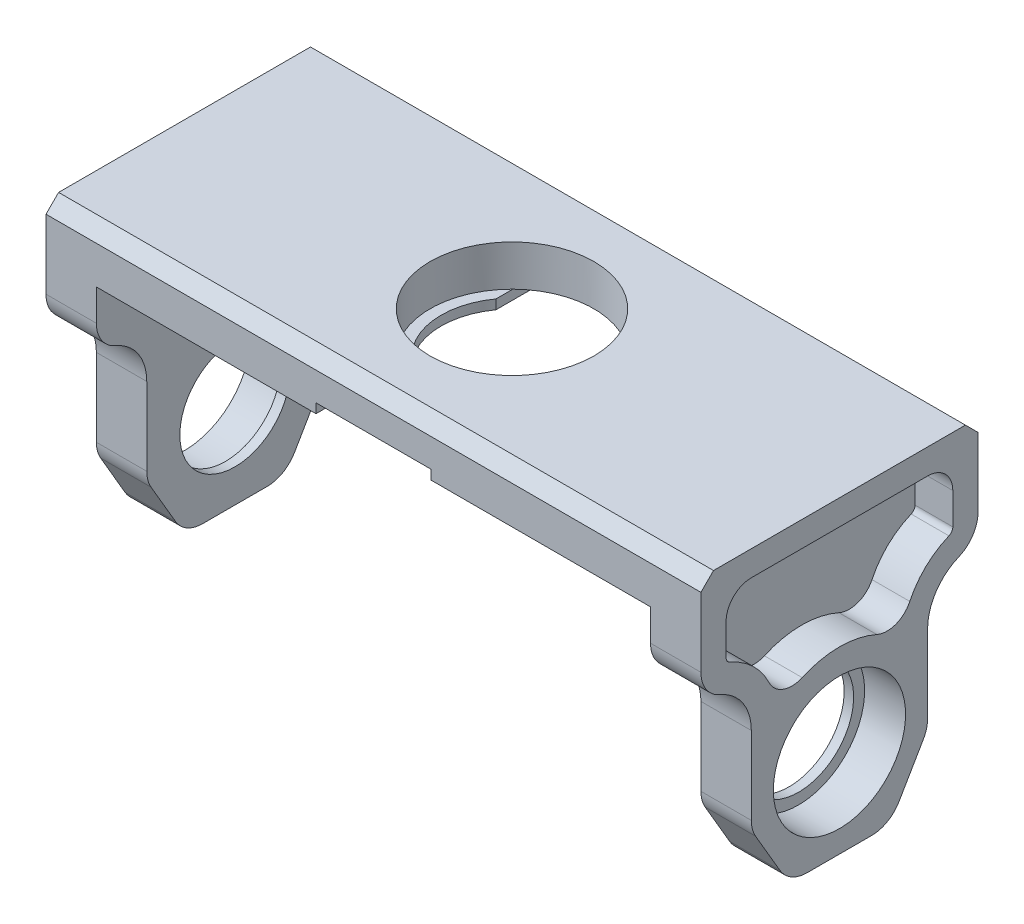
SolidWorks part; units mm, degrees
ref_plane "Front Plane" through (0, 0, 0) normal (0, 0, 1) x (1, 0, 0)
ref_plane "Top Plane" through (0, 0, 0) normal (0, 1, 0) x (1, 0, 0)
ref_plane "Right Plane" through (0, 0, 0) normal (1, 0, 0) x (0, 0, -1)
sketch "Sketch1" plane through (0, 0, 0) normal (0, 0, 1) x (1, 0, 0)
  line L0 (44, 0) -> (-44, 0)
  line L1 (-44, 0) -> (-44, -41)
  line L2 (-44, -41) -> (-52, -41)
  line L3 (-52, -41) -> (-52, 8)
  line L4 (-52, 8) -> (52, 8)
  line L5 (52, 8) -> (52, -41)
  line L6 (52, -41) -> (44, -41)
  line L7 (44, -41) -> (44, 0)
  point P4 (0, 0)
  dimension "D1" = 88
  dimension "D2" = 8
  dimension "D3" = 8
  dimension "D4" = 49
extrude "Boss-Extrude1" add sketch "Sketch1" along normal blind 44
sketch "Sketch4" plane through (-52, 0, 0) normal (-1, 0, 0) x (0, 0, 1)
  line L0 (0, -27) -> (22, -27) construction
  line L1 (0, 8) -> (0, -41) construction
  line L2 (22, -27) -> (44, -27) construction
  line L3 (44, 8) -> (44, -41) construction
  line L5 (44, -41) -> (0, -41) construction
  point P0 (22, -27)
  dimension "D1" = 14
hole_wizard "Ø21.0 (21) Diameter Hole1" positions "Sketch4" profile "Sketch3" hole size "Ø21.0" standard "DIN" end condition through all
sketch "Sketch3" plane through (-52, -27, 22) normal (0, 1, 0) x (0, 0, 1)
  line L0 (0, 0) -> (0, 104)
  line L1 (0, 104) -> (10.5, 104)
  line L2 (10.5, 104) -> (10.5, 0)
  line L5 (10.5, 0) -> (0, 0)
  line L11 (0, -6.35) -> (0, 107.95) construction
  dimension "Thru Hole Dia." = 21
  dimension "Thru Hole Depth" = 104
sketch "Sketch8" plane through (0, 8, 0) normal (0, 1, 0) x (1, 0, 0)
  line L0 (-52, -22) -> (0, -22) construction
  line L1 (-52, -44) -> (-52, 0) construction
  line L2 (0, -22) -> (52, -22) construction
  line L3 (52, -44) -> (52, 0) construction
  line L5 (0, 0) -> (0, -22) construction
  line L6 (0, -22) -> (0, -44) construction
  line L7 (52, -44) -> (-52, -44) construction
  point P2 (0, -22)
  point P23 (0, -22)
hole_wizard "Ø26.0 (26) Diameter Hole1" positions "Sketch8" profile "Sketch6" hole size "Ø26.0" standard "DIN" end condition through all
sketch "Sketch6" plane through (0, 8, 22) normal (1, 0, 0) x (0, 0, 1)
  line L0 (0, 0) -> (0, 49)
  line L1 (0, 49) -> (13, 49)
  line L2 (13, 49) -> (13, 0)
  line L5 (13, 0) -> (0, 0)
  line L11 (0, -6.35) -> (0, 107.95) construction
  dimension "Thru Hole Dia." = 26
  dimension "Thru Hole Depth" = 49
sketch "Sketch9" plane through (44, 0, 0) normal (-1, 0, 0) x (0, 0, 1)
  circle A0 centre (22, -27) radius 10.5 construction
  circle A1 centre (22, -27) radius 10.5
  circle A2 centre (22, -27) radius 8.75
  dimension "D1" = 1.75
extrude "Boss-Extrude2" add sketch "Sketch9" against normal blind 1.5
extrude "Boss-Extrude3" add sketch "Sketch9<2>" along normal blind 1.5 from surface starting at face at (-44, -37.5, 22)
sketch "Sketch9<2>" plane through (44, 0, 0) normal (-1, 0, 0) x (0, 0, 1) same geometry as "Sketch9"
sketch "Sketch16" plane through (0, 0, 0) normal (0, 1, 0) x (1, 0, 0)
  circle A0 centre (0, -22) radius 13 construction
  circle A1 centre (0, -22) radius 13
  circle A2 centre (0, -22) radius 11.25
  dimension "D1" = 1.75
extrude "Boss-Extrude4" add sketch "Sketch16" along normal blind 1.5
sketch "Sketch17" plane through (0, 0, 44) normal (0, 0, 1) x (1, 0, 0)
  line L0 (-44, 0) -> (44, 0) construction
  line L1 (-9.125, 0) -> (9.125, 0)
  line L2 (-9.125, 0) -> (-9.125, 1.5)
  line L3 (-9.125, 1.5) -> (9.125, 1.5)
  line L4 (9.125, 0) -> (9.125, 1.5)
  line L5 (0, 1.5) -> (0, 0) construction
  dimension "D1" = 18.25
  dimension "D2" = 1.5
extrude "Cut-Extrude1" cut sketch "Sketch17" against normal through all
sketch "Sketch19" plane through (-52, 0, 0) normal (-1, 0, 0) x (0, 0, 1)
  line L0 (0, 8) -> (0, -41) construction
  line L1 (44, 8) -> (0, 8) construction
  line L2 (0, -17) -> (14, -41)
  line L3 (44, -41) -> (0, -41) construction
  line L4 (14, -41) -> (0, -41)
  line L5 (0, -41) -> (0, -17)
  line L6 (8, -17) -> (8, -30.7143)
  line L7 (22, -27) -> (22, -10.1382) construction
  line L8 (36, -17) -> (36, -30.7143)
  line L9 (30, -41) -> (44, -41)
  line L10 (44, -17) -> (30, -41)
  line L11 (44, -41) -> (44, -17)
  circle A0 centre (0, -17) radius 8
  circle A1 centre (44, -17) radius 8
  line M3 (0, 8) -> (0, -41)
  line M6 (44, -41) -> (44, 8)
  line M8 (0, -41) -> (44, -41)
  dimension "D1" = 16
  dimension "D2" = 25
  dimension "D3" = 14
extrude "Cut-Extrude3" cut sketch "Sketch19" against normal through all contours L2 A0 M3 | A0 L5 L2 M8 | A0 L2 L6 | L10 A1 L8 | A1 L10 M6 | A1 L10 M6 M8 | A1 | L9 L11 L10 | A0 region at (-52, -34.2202, 38.9653) region at (-52, -34.2202, 5.0347) region at (-52, -24.7293, 6.7544) region at (-52, -15.9718, 3.8034) region at (-52, -24.7293, 37.2456) region at (-52, -15.9718, 40.1966)
fillet "Fillet3" radius 5 12 edges at (48, -9, 0) (-48, -9, 0) (48, -30.7143, 8) (-48, -30.7143, 8) (-48, -9, 44) (48, -9, 44) (48, -30.7143, 36) (-48, -30.7143, 36) (-48, -41, 14) (48, -41, 14) (48, -41, 30) (-48, -41, 30)
ref_plane "Plane1" through (0, 0, 22) normal (0, 0, 1) x (1, 0, 0)
sketch "Sketch20" plane through (0, 0, 22) normal (0, 0, 1) x (1, 0, 0)
  line L0 (-36, 0) -> (-44, -8)
  line L1 (-44, 0) -> (-9.125, 0) construction
  line L2 (-44, 0) -> (-9.125, 0) construction
  line L3 (-44, -35.75) -> (-44, -18.25) construction
  dimension "D1" = 45
  dimension "D2" = 8
rib "Rib1" sketch "Sketch20" sketch "Sketch20" thickness 20 extrusion direction parallel to sketch draft on no parameters "D1"=20
sketch "Sketch21" plane through (0, 0, 22) normal (0, 0, 1) x (1, 0, 0)
  line L0 (36, 0) -> (44, -8)
  line L1 (9.125, 0) -> (44, 0) construction
  line L2 (44, -18.25) -> (44, -35.75) construction
  dimension "D1" = 45
  dimension "D2" = 8
rib "Rib2" sketch "Sketch21" sketch "Sketch21" thickness 20 extrusion direction parallel to sketch draft on no parameters "D1"=20
sketch "Sketch22" plane through (0, 0, 0) normal (0, -1, 0) x (1, 0, 0)
  line L0 (-36, 32) -> (-36, 12) construction
  line L1 (-36, 41) -> (-16, 41)
  line L2 (-36, 41) -> (-36, 3)
  line L3 (-36, 3) -> (-16, 3)
  line L4 (-16, 41) -> (-16, 3)
  line L5 (-44, 44) -> (-9.125, 44) construction
  line L6 (0, 22) -> (0, 54.9739) construction
  line L7 (36, 3) -> (16, 3)
  line L8 (16, 41) -> (16, 3)
  line L9 (36, 41) -> (16, 41)
  line L10 (36, 41) -> (36, 3)
  arc A0 (-9.125, 31.2593) -> (-9.125, 12.7407) centre (0, 22) ccw construction
  arc A1 (-9.125, 31.2593) -> (-9.125, 12.7407) centre (0, 22) ccw construction
  point P7 (-13, 22)
  point P10 (-16, 22)
  dimension "D1" = 3
  dimension "D2" = 3
extrude "Cut-Extrude4" cut sketch "Sketch22" against normal blind 6
sketch "Sketch23" plane through (-52, 0, 0) normal (-1, 0, 0) x (0, 0, 1)
  line L16 (40, 4) -> (4, 4)
  line L17 (4, 4) -> (4, -5)
  line L18 (12, -17) -> (12, -29.3625)
  line L19 (12.1362, -29.8664) -> (16.0081, -36.5039)
  line L20 (16.8719, -37) -> (27.1281, -37)
  line L21 (27.9919, -36.5039) -> (31.8638, -29.8664)
  line L22 (32, -29.3625) -> (32, -17)
  line L23 (40, -5) -> (40, 4)
  line L24 (40, 4) -> (4, 4)
  line L25 (4, 4) -> (4, -5)
  line L26 (12, -17) -> (12, -29.3625)
  line L27 (12.1362, -29.8664) -> (16.0081, -36.5039)
  line L28 (16.8719, -37) -> (27.1281, -37)
  line L29 (27.9919, -36.5039) -> (31.8638, -29.8664)
  line L30 (32, -29.3625) -> (32, -17)
  line L31 (40, -5) -> (40, 4)
  circle A10 centre (22, -27) radius 14.5
  circle A11 centre (22, -27) radius 14.5
  arc A16 (4, -5) -> (4.6154, -5.9231) centre (5, -5) ccw
  arc A17 (12, -17) -> (4.6154, -5.9231) centre (0, -17) ccw
  arc A18 (12, -29.3625) -> (12.1362, -29.8664) centre (13, -29.3625) ccw
  arc A19 (16.0081, -36.5039) -> (16.8719, -37) centre (16.8719, -36) ccw
  arc A20 (27.1281, -37) -> (27.9919, -36.5039) centre (27.1281, -36) ccw
  arc A21 (31.8638, -29.8664) -> (32, -29.3625) centre (31, -29.3625) ccw
  arc A22 (39.3846, -5.9231) -> (32, -17) centre (44, -17) ccw
  arc A23 (39.3846, -5.9231) -> (40, -5) centre (39, -5) ccw
  arc A24 (4, -5) -> (4.6154, -5.9231) centre (5, -5) ccw
  arc A25 (12, -17) -> (4.6154, -5.9231) centre (0, -17) ccw
  arc A26 (12, -29.3625) -> (12.1362, -29.8664) centre (13, -29.3625) ccw
  arc A27 (16.0081, -36.5039) -> (16.8719, -37) centre (16.8719, -36) ccw
  arc A28 (27.1281, -37) -> (27.9919, -36.5039) centre (27.1281, -36) ccw
  arc A29 (31.8638, -29.8664) -> (32, -29.3625) centre (31, -29.3625) ccw
  arc A30 (39.3846, -5.9231) -> (32, -17) centre (44, -17) ccw
  arc A31 (39.3846, -5.9231) -> (40, -5) centre (39, -5) ccw
  dimension "D1" = 4
  dimension "D2" = 4
extrude "Cut-Extrude5" cut sketch "Sketch23" against normal blind 6 and the other way through all contours A30 A31 L31 L24 L25 A24 A25 A11 region at (-52, -4.0807, 22)
extrude "Cut-Extrude6" cut sketch "Sketch23<3>" along normal blind 6 from surface contours A30 A31 L31 L24 L25 A24 A25 A11 region at (-52, -4.0807, 22) starting at face at (52, -20.5901, 22)
sketch "Sketch23<3>" plane through (-52, 0, 0) normal (-1, 0, 0) x (0, 0, 1) same geometry as "Sketch23"
fillet "Fillet4" radius 4 16 edges at (-49, -16.5096, 11.99) (-49, -16.5096, 32.01) (49, -16.5096, 32.01) (49, -16.5096, 11.99) (49, 4, 4) (49, 4, 40) (-49, 4, 40) (-49, 4, 4) (36, 3, 3) (-16, 3, 3) (36, 3, 41) (-16, 3, 41) (-36, 3, 3) (16, 3, 3) (16, 3, 41) (-36, 3, 41)
chamfer "Chamfer1" distance 2 angle 45 2 edges at (0, 8, 44) (0, 8, 0)
